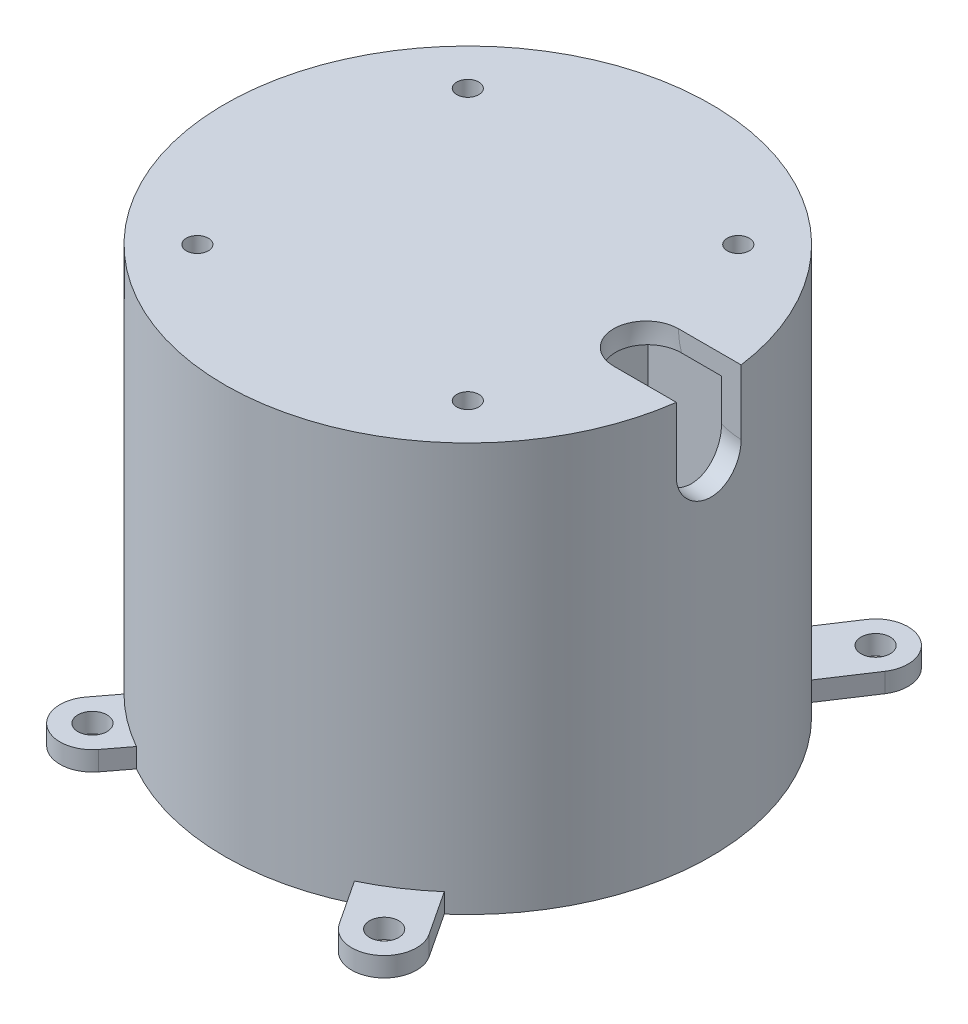
SolidWorks part; units mm, degrees
ref_plane "Front Plane" through (0, 0, 0) normal (0, 0, 1) x (1, 0, 0)
ref_plane "Top Plane" through (0, 0, 0) normal (0, 1, 0) x (1, 0, 0)
ref_plane "Right Plane" through (0, 0, 0) normal (1, 0, 0) x (0, 0, -1)
sketch "Sketch1" plane through (0, 0, 0) normal (0, 1, 0) x (1, 0, 0)
  circle A6 centre (0, 0) radius 37.5
  dimension "D1" = 75
extrude "Boss-Extrude2" add sketch "Sketch1" against normal blind 3
sketch "Sketch2" plane through (0, -3, 0) normal (0, -1, 0) x (1, 0, 0)
  line L4 (0, 32.7824) -> (0, 0) construction
  circle A0 centre (0, 0) radius 34.5
  circle A1 centre (0, 0) radius 37.5
  circle A2 centre (0, 0) radius 37.5
  dimension "D2" = 3
  dimension "D1" = 0
extrude "Boss-Extrude3" add sketch "Sketch2" along normal blind 60
sketch "Sketch3" plane through (0, -3, 0) normal (0, -1, 0) x (1, 0, 0)
  line L0 (13.5, 34.9857) -> (13.5, 31.749)
  line L8 (13.5, 31.749) -> (-13.5, 31.749)
  line L9 (-13.5, 31.749) -> (-13.5, 34.9857)
  line L10 (0, 0) -> (-12.0832, 0) construction
  line L11 (-13.5, -31.749) -> (-13.5, -34.9857)
  line L12 (13.5, -31.749) -> (-13.5, -31.749)
  line L13 (13.5, -34.9857) -> (13.5, -31.749)
  circle A4 centre (0, 0) radius 37.5 construction
  arc A5 (13.5, 34.9857) -> (-13.5, 34.9857) centre (0, 0) ccw
  circle A6 centre (0, 0) radius 34.5 construction
  arc A7 (13.5, -34.9857) -> (-13.5, -34.9857) centre (0, 0) cw
  dimension "D1" = 27
extrude "Boss-Extrude4" add sketch "Sketch3" along normal up to surface (60 mm away) up to face at (0, -63, -37.5)
sketch "Sketch4" plane through (0, 0, 0) normal (0, 0, 1) x (1, 0, 0)
  line L0 (-12.625, -14.83) -> (-12.625, -9.67) construction
  line L1 (12.625, -9.67) -> (12.625, -14.83) construction
  line L2 (-12.625, -14.83) -> (-12.625, -9.67) construction
  line L3 (12.625, -9.67) -> (12.625, -14.83) construction
  line L4 (-12.825, -3) -> (-12.825, -14.83)
  line L5 (-12.125, -17.0499) -> (-12.125, -19.0499)
  line L6 (-12.125, -19.0499) -> (-17.825, -19.0499)
  line L7 (-17.825, -19.0499) -> (-17.825, -3)
  line L8 (-17.825, -3) -> (-12.825, -3)
  line L10 (0, 0) -> (0, -13.0317) construction
  line L11 (17.825, -19.0499) -> (17.825, -3)
  line L12 (12.125, -19.0499) -> (17.825, -19.0499)
  line L13 (12.125, -17.0499) -> (12.125, -19.0499)
  line L14 (12.825, -3) -> (12.825, -14.83)
  line L15 (17.825, -3) -> (12.825, -3)
  line L16 (13.5, -3) -> (34.5, -3) construction
  arc A0 (-12.825, -14.83) -> (-12.125, -17.0499) centre (-8.955, -14.83) ccw
  arc A2 (12.825, -14.83) -> (12.125, -17.0499) centre (8.955, -14.83) cw
  arc A3 (-12.625, -14.83) -> (-8.955, -18.5) centre (-8.955, -14.83) ccw construction
  dimension "D1" = 0.2
  dimension "D2" = 0.7
  dimension "D3" = 2
  dimension "D4" = 5
extrude "Boss-Extrude5" add sketch "Sketch4" along normal mid plane 20
ref_plane "Plane1" through (37.5, 0, 0) normal (1, 0, 0) x (0, 0, -1)
sketch "Sketch7" plane through (0, -63, 0) normal (0, -1, 0) x (1, 0, 0)
  circle A0 centre (0, 0) radius 37.5
  circle A1 centre (0, 0) radius 31.5
  circle A2 centre (0, 0) radius 37.5 construction
  dimension "D1" = 6
extrude "Boss-Extrude7" add sketch "Sketch7" against normal blind 3
hole_wizard "M3 Clearance Hole1" positions "Sketch8" profile "Sketch10" hole size "M3" standard "ANSI Metric" end condition through all
sketch "Sketch8" plane through (0, -3, 0) normal (0, -1, 0) x (-1, 0, 0)
  circle A2 centre (20.8597, -20.8597) radius 1.6
  circle A3 centre (20.8597, -20.8597) radius 1.6
  circle A6 centre (-20.8597, -20.8597) radius 1.6
  circle A7 centre (-20.8597, -20.8597) radius 1.6
  circle A10 centre (-20.8597, 20.8597) radius 1.6
  circle A11 centre (-20.8597, 20.8597) radius 1.6
  circle A14 centre (20.8597, 20.8597) radius 1.6
  circle A15 centre (20.8597, 20.8597) radius 1.6
  point P5 (20.8597, -20.8597)
  point P12 (-20.8597, -20.8597)
  point P19 (-20.8597, 20.8597)
  point P26 (20.8597, 20.8597)
  dimension "D1" = 0
  dimension "D2" = 0
  dimension "D3" = 0
  dimension "D4" = 0
sketch "Sketch10" plane through (-20.8597, -3, 20.8597) normal (1, 0, 0) x (0, 0, -1)
  line L0 (0, 0) -> (0, 3)
  line L1 (0, 3) -> (1.7, 3)
  line L2 (1.7, 3) -> (1.7, 0)
  line L5 (1.7, 0) -> (0, 0)
  line L11 (0, -6.35) -> (0, 107.95) construction
  dimension "Thru Hole Dia." = 3.4
  dimension "Thru Hole Depth" = 3
sketch "Sketch11" plane through (0, 0, 0) normal (0, 1, 0) x (1, 0, 0)
  line L0 (37.5, -5) -> (27.5, -5)
  line L1 (27.5, 5) -> (37.5, 5)
  line L2 (27.5, 0) -> (0, 0) construction
  line L3 (37.5, -5) -> (37.5, 5)
  arc A0 (27.5, -5) -> (27.5, 5) centre (27.5, 0) cw
  circle A1 centre (0, 0) radius 37.5 construction
  point P2 (22.5, 0)
  point P4 (37.5, 0)
  dimension "D3" = 15
  dimension "D2" = 10
revolve "Cut-Revolve1" cut sketch "Sketch11" angle 360 about L3
sketch "Sketch14" plane through (0, -63, 0) normal (0, -1, 0) x (1, 0, 0)
  line L0 (25, 37.9) -> (25, 32.9)
  line L1 (25, 32.9) -> (-25, 32.9)
  line L2 (0, -32.9) -> (0, 32.9)
  line L3 (0, 0) -> (13.3551, 0) construction
  line L4 (25, -32.9) -> (-25, -32.9)
  line L5 (25, -37.9) -> (25, -32.9)
  point P7 (0, 0)
  dimension "D1" = 50
  dimension "D2" = 5
  dimension "D3" = 65.8
sketch "Sketch15" plane through (0, -63, 0) normal (0, -1, 0) x (1, 0, 0)
  line L0 (24.6379, 28.2705) -> (29.1738, 35.1469)
  line L1 (20.8262, 40.6531) -> (16.2904, 33.7768)
  line L2 (-26.4668, 26.5661) -> (-28.981, 29.8749)
  line L3 (-21.019, 35.9251) -> (-18.5047, 32.6163)
  line L5 (-25, 32.9) -> (0, 0) construction
  line L6 (0, 0) -> (25, 37.9) construction
  line L7 (0, 0) -> (-26.4668, 0) construction
  line L8 (-21.019, -35.9251) -> (-18.5047, -32.6163)
  line L9 (-26.4668, -26.5661) -> (-28.981, -29.8749)
  line L10 (24.6379, -28.2705) -> (29.1738, -35.1469)
  line L11 (20.8262, -40.6531) -> (16.2904, -33.7768)
  circle A0 centre (0, 0) radius 37.5 construction
  arc A1 (29.1738, 35.1469) -> (20.8262, 40.6531) centre (25, 37.9) ccw
  arc A2 (-18.5047, 32.6163) -> (-26.4668, 26.5661) centre (0, 0) ccw
  arc A3 (-28.981, 29.8749) -> (-21.019, 35.9251) centre (-25, 32.9) cw
  arc A4 (24.6379, 28.2705) -> (16.2904, 33.7768) centre (0, 0) ccw
  arc A5 (-28.981, -29.8749) -> (-21.019, -35.9251) centre (-25, -32.9) ccw
  arc A6 (-18.5047, -32.6163) -> (-26.4668, -26.5661) centre (0, 0) cw
  arc A7 (29.1738, -35.1469) -> (20.8262, -40.6531) centre (25, -37.9) cw
  arc A8 (24.6379, -28.2705) -> (16.2904, -33.7768) centre (0, 0) cw
  dimension "D1" = 10
extrude "Boss-Extrude8" add sketch "Sketch15" against normal blind 3
hole_wizard "#8 Clearance Hole1" positions "Sketch16" profile "Sketch17" hole size "#8" standard "ANSI Inch" end condition through all
sketch "Sketch16" plane through (0, -63, 0) normal (0, -1, 0) x (-1, 0, 0)
  point P0 (-25, -37.9)
  point P3 (25, -32.9)
  point P6 (-25, 37.9)
  point P9 (25, 32.9)
sketch "Sketch17" plane through (25, -63, 37.9) normal (1, 0, 0) x (0, 0, -1)
  line L0 (0, 0) -> (0, 63)
  line L1 (0, 63) -> (2.2479, 63)
  line L2 (2.2479, 63) -> (2.2479, 0)
  line L5 (2.2479, 0) -> (0, 0)
  line L11 (0, -6.35) -> (0, 107.95) construction
  dimension "Thru Hole Dia." = 4.4958
  dimension "Thru Hole Depth" = 63
sketch "Sketch18" plane through (0, -3, 0) normal (0, -1, 0) x (1, 0, 0)
  line L1 (-12.825, 20) -> (12.825, 20)
  line L2 (-12.825, 20) -> (-12.825, -20)
  line L3 (-12.825, -20) -> (12.825, -20)
  line L4 (12.825, 20) -> (12.825, -20)
  line L5 (-12.825, 20) -> (12.825, -20) construction
  line L6 (-12.825, -20) -> (12.825, 20) construction
  point P0 (0, 0)
  dimension "D1" = 40
extrude "Boss-Extrude9" add sketch "Sketch18" along normal blind 3
sketch "Sketch19" plane through (0, 0, -31.749) normal (0, 0, 1) x (1, 0, 0)
  line L0 (8.955, -18.5) -> (-8.955, -18.5) construction
  line L1 (10.75, -5.5) -> (-10.75, -5.5)
  line L2 (10.75, -5.5) -> (10.75, -18.5)
  line L3 (10.75, -18.5) -> (-10.75, -18.5)
  line L4 (-10.75, -5.5) -> (-10.75, -18.5)
  line L5 (0, 0) -> (0, -5.5) construction
  line L6 (-8.955, -6) -> (5.61, -6) construction
  line L7 (-8.955, -6) -> (5.61, -6) construction
  dimension "D1" = 1
  dimension "D2" = 21.5
extrude "Cut-Extrude4" cut sketch "Sketch19" against normal through all
fillet "Fillet2" radius 2 4 edges at (-10.75, -5.5, -33.8376) (10.75, -5.5, -33.8376) (10.75, -18.5, -33.8376) (-10.75, -18.5, -33.8376)
